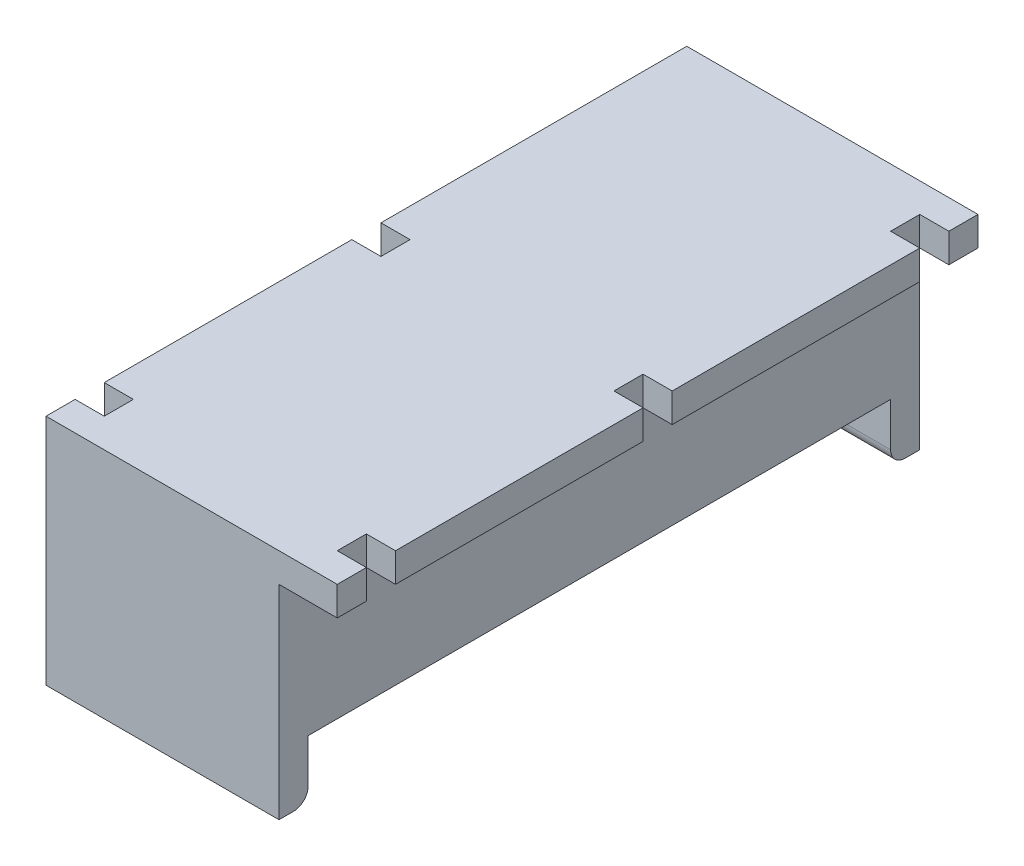
SolidWorks part; units mm, degrees
ref_plane "Front Plane" through (0, 0, 0) normal (0, 0, 1) x (1, 0, 0)
ref_plane "Top Plane" through (0, 0, 0) normal (0, 1, 0) x (1, 0, 0)
ref_plane "Right Plane" through (0, 0, 0) normal (1, 0, 0) x (0, 0, -1)
sketch "Sketch2" plane through (0, 0, 0) normal (0, 1, 0) x (1, 0, 0)
  line L0 (-22.5, -50) -> (27.5, -50)
  line L1 (-22.5, 60) -> (27.5, 60)
  line L2 (-22.5, 60) -> (-22.5, -50)
  line L4 (27.5, 60) -> (27.5, -50)
  line L5 (27.5, -50) -> (22.5, -50)
  line L6 (22.5, -50) -> (22.5, 60)
  line L7 (-17.5, -50) -> (-17.5, 60)
  line L8 (27.5, 60) -> (27.5, 55)
  line L9 (27.5, 55) -> (-17.5, 55)
  line L10 (27.5, -50) -> (27.5, -45)
  line L11 (27.5, -45) -> (-17.5, -45)
  point P0 (0, 0)
  dimension "D1" = 110
  dimension "D2" = 50
  dimension "D3" = 5
extrude "Boss-Extrude1" add sketch "Sketch2" against normal blind 30 contours L0 L7 L1 L2 | L9 L6 L1 L7 | L9 L4 L1 L6 | L11 L4 L9 L6 | L4 L11 L6 L0 | L6 L11 L7 L0 region at (-20, 0, -5) region at (2.5, 0, 47.5) region at (25, 0, 47.5) region at (2.5, 0, -57.5) region at (25, 0, -5) region at (25, 0, -57.5)
sketch "Sketch3" plane through (-22.5, 0, 0) normal (-1, 0, 0) x (0, 0, 1)
  line L0 (-60, -30) -> (-40, -30)
  line L2 (-40, -30) -> (-30, -30)
  line L3 (-60, -30) -> (50, -30) construction
  line L4 (-30, -30) -> (-30, -20)
  line L5 (-30, -20) -> (-40, -20)
  line L6 (-40, -20) -> (-40, -30)
  line L7 (-35, -30) -> (-35, -25)
  line L8 (-35, -25) -> (-40, -25)
  line L10 (-38, -22) -> (-32, -22)
  line L11 (-38, -22) -> (-38, -28)
  line L12 (-38, -28) -> (-32, -28)
  line L13 (-32, -22) -> (-32, -28)
  line L14 (-38, -22) -> (-32, -28) construction
  line L15 (-38, -28) -> (-32, -22) construction
  dimension "D1" = 20
  dimension "D2" = 6
  dimension "D3" = 6
extrude "Cut-Extrude1" cut sketch "Sketch3" against normal blind 5 contours L13 L10 L11 L8 L7 L12 | L11 L12 L7 L8 region at (-22.5, -26.5, -36.5) region at (-22.5, -24.5, -34.5)
extrude "Boss-Extrude2" add sketch "Sketch2<4>" against normal blind 5 contours L11 L6 L9 L7 region at (2.5, 0, -5)
sketch "Sketch2<4>" plane through (0, 0, 0) normal (0, 1, 0) x (1, 0, 0) same geometry as "Sketch2"
sketch "Sketch4" plane through (0, 0, 0) normal (0, 1, 0) x (1, 0, 0)
  line L0 (-22.5, 60) -> (27.5, 60)
  line L1 (27.5, 60) -> (27.5, -50)
  line L2 (27.5, -50) -> (-22.5, -50)
  line L3 (-22.5, -50) -> (-22.5, 60)
sketch "Sketch5" plane through (0, -30, 0) normal (0, -1, 0) x (1, 0, 0)
  line L0 (-22.5, 50) -> (-22.5, 45)
  line L1 (-22.5, 50) -> (-22.5, -60) construction
  line L2 (-22.5, 45) -> (17.5, 45)
  line L3 (22.5, 45) -> (-17.5, 45) construction
  line L4 (17.5, 45) -> (17.5, -55)
  line L5 (22.5, -55) -> (-17.5, -55) construction
  line L6 (17.5, -55) -> (-22.5, -55)
  line L7 (-22.5, 45) -> (-22.5, 40)
  line L8 (-22.5, 40) -> (12.5, 40)
  line L9 (12.5, 40) -> (12.5, -50)
  line L10 (12.5, -50) -> (-22.5, -50)
  line L11 (-17.5, -55) -> (-17.5, -50)
  line L12 (-17.5, 45) -> (-17.5, -55) construction
  line L13 (-22.5, 50) -> (27.5, 50)
  line L14 (27.5, 50) -> (27.5, -60)
  line L15 (27.5, -60) -> (-22.5, -60)
  line L16 (-22.5, -60) -> (-22.5, -55)
  line L17 (-17.5, 45) -> (-17.5, 40)
  line L18 (-22.5, 45) -> (-22.5, 40)
  line L19 (-22.5, -50) -> (-22.5, -55)
  line M1 (22.5, -55) -> (-17.5, -55)
  line M2 (-17.5, -55) -> (-17.5, 45)
  line M3 (-17.5, 45) -> (22.5, 45)
  line M4 (22.5, 45) -> (22.5, -55)
  line M5 (27.5, 50) -> (-22.5, 50)
  line M6 (-22.5, 50) -> (-22.5, -60)
  line M7 (-22.5, -60) -> (27.5, -60)
  line M8 (27.5, -60) -> (27.5, 50)
extrude "Cut-Extrude2" cut sketch "Sketch5" against normal blind 25 contours L6 L2 M1 M6 M7 M8 M5 M3 M4 region at (2.5, -30, 48.7917)
extrude "Boss-Extrude3" add sketch "Sketch5<3>" against normal blind 25 contours L9 L10 L4 L8 M2 M1 M3 region at (0, -30, 43.9405)
sketch "Sketch5<3>" plane through (0, -30, 0) normal (0, -1, 0) x (1, 0, 0) same geometry as "Sketch5"
sketch "Sketch10" plane through (0, -5, 0) normal (0, -1, 0) x (1, 0, 0)
  line L0 (-22.5, 50) -> (17.5, 50)
  line L3 (17.5, 45) -> (-22.5, 45)
  line L4 (-22.5, 45) -> (-22.5, 50)
  line L7 (17.5, -60) -> (-22.5, -60)
  line L8 (-22.5, -60) -> (-22.5, -55)
  line L9 (-22.5, -55) -> (17.5, -55)
  line L10 (17.5, 45) -> (17.5, 50)
  line L11 (17.5, -55) -> (17.5, -60)
extrude "Boss-Extrude4" add sketch "Sketch10" along normal blind 35
sketch "Sketch11" plane through (0, 0, 0) normal (0, 1, 0) x (1, 0, 0)
  line L0 (-22.5, 60) -> (27.5, 60)
  line L1 (27.5, 60) -> (27.5, -50)
  line L2 (27.5, -50) -> (-22.5, -50)
  line L3 (-22.5, -50) -> (-22.5, 60)
  line L4 (27.5, 60) -> (27.5, 55)
  line L5 (27.5, 55) -> (-22.5, 55)
  line L6 (27.5, 60) -> (22.5, 60)
  line L7 (22.5, 60) -> (22.5, -50)
  line L8 (27.5, -50) -> (27.5, -45)
  line L9 (27.5, -45) -> (-22.5, -45)
  line L10 (27.5, -45) -> (27.5, -40)
  line L11 (22.5, -40) -> (27.5, -40)
  line L12 (27.5, -45) -> (22.5, -45)
  line L13 (22.5, -40) -> (22.5, -45)
  line L14 (27.5, -40) -> (27.5, -45)
  line L19 (22.5, -40) -> (24, -40)
  line L20 (22.5, -40) -> (22.5, -41.5)
  line L21 (27.5, -40) -> (27.5, -45)
  line L22 (27.5, -45) -> (22.5, -45)
  line L23 (22.5, -45) -> (22.5, -40)
  line L24 (27.5, -45) -> (22.5, -45)
  line L29 (-22.5, -45) -> (-17.5, -45)
  line L30 (-17.5, -40) -> (-17.5, -45)
  line L31 (22.5, -40) -> (23.5, -40)
  line L32 (22.5, -40) -> (22.5, -41)
  line L33 (22.5, -45) -> (22.5, 5)
  line L38 (27.5, -40) -> (22.5, -40)
  line L39 (27.5, -40) -> (27.5, -45)
  line L40 (22.5, -20) -> (24, -20)
  line L45 (27.5, 55) -> (27.5, -45)
  line L46 (27.5, 5) -> (27.5, 7.5)
  line L47 (27.5, 5) -> (27.5, 2.5)
  line L48 (27.5, 2.5) -> (22.5, 2.5)
  line L49 (22.5, 2.5) -> (22.5, 7.5)
  line L50 (22.5, 7.5) -> (27.5, 7.5)
  line L51 (27.5, 55) -> (27.5, 50)
  line L52 (27.5, 50) -> (22.5, 50)
  line L53 (22.5, 50) -> (22.5, 55)
  line L54 (22.5, 55) -> (27.5, 55)
  line L55 (27.5, 55) -> (-22.5, 55)
  line L56 (2.5, 55) -> (2.5, 50)
  line L57 (22.5, -40) -> (27.5, -40)
  line L58 (27.5, -45) -> (27.5, -40)
  line L59 (27.5, -45) -> (22.5, -45)
  line L60 (22.5, -40) -> (22.5, -45)
  line L61 (27.5, -45) -> (22.5, -45)
  line L62 (22.5, -40) -> (22.5, -45)
  line L63 (27.5, -40) -> (22.5, -45) construction
  line L64 (27.5, -45) -> (22.5, -40) construction
  line L65 (-22.5, -40) -> (-17.5, -40)
  line L66 (-22.5, -40) -> (-22.5, -45)
  line L67 (-17.5, 2.5) -> (-17.5, 7.5)
  line L68 (-22.5, 2.5) -> (-17.5, 2.5)
  line L69 (-22.5, 5) -> (-22.5, 2.5)
  line L70 (-22.5, 5) -> (-22.5, 7.5)
  line L71 (-17.5, 7.5) -> (-22.5, 7.5)
  line L72 (-17.5, 55) -> (-22.5, 55)
  line L73 (-17.5, 50) -> (-17.5, 55)
  line L74 (-22.5, 50) -> (-17.5, 50)
  line L75 (-22.5, 55) -> (-22.5, 50)
  line M24 (-22.5, 60) -> (-22.5, -50)
extrude "Cut-Extrude5" cut sketch "Sketch11" against normal blind 6 contours L52 L45 L5 L7 | L50 L7 L48 L45 | L11 L7 L23 L13 L9 L1 L19 region at (25, 0, -52.5) region at (25, 0, -5) region at (25, 0, 42.5)
extrude "Cut-Extrude6" cut sketch "Sketch11<4>" against normal blind 4.99 contours L67 L71 L68 M24 | L65 L9 L30 M24 region at (-20, 0, -5) region at (-20, 0, 42.5)
sketch "Sketch11<4>" plane through (0, 0, 0) normal (0, 1, 0) x (1, 0, 0) same geometry as "Sketch11"
fillet "Fillet1" radius 2.5 2 edges at (-2.5, -40, -55) (-2.5, -40, 45)
